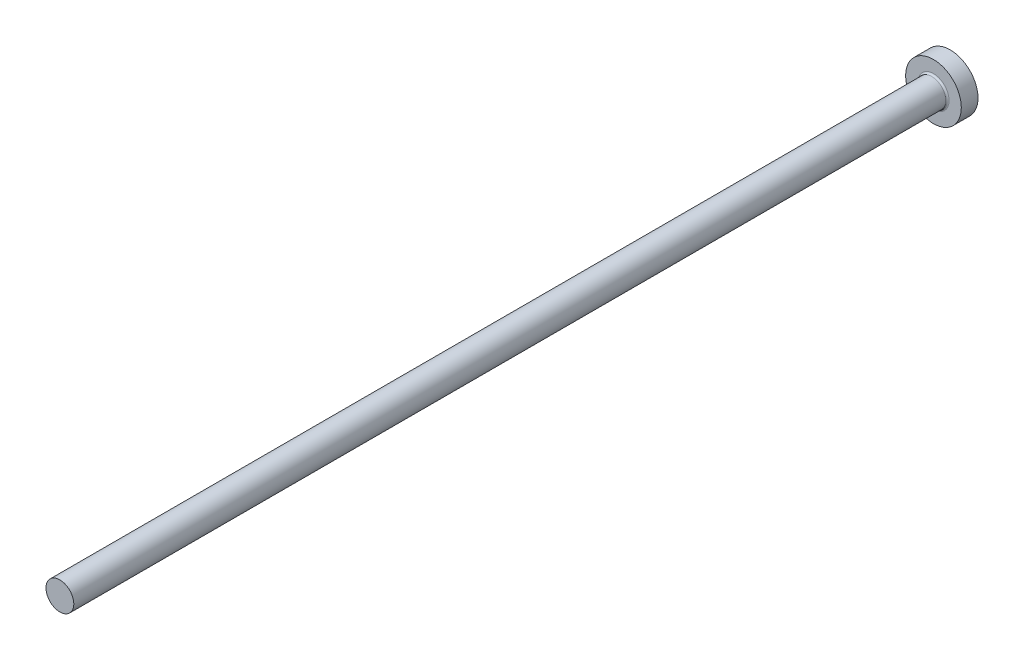
SolidWorks part; units mm, degrees
ref_plane "Płaszczyzna przednia" through (0, 0, 0) normal (0, 0, 1) x (1, 0, 0)
ref_plane "Płaszczyzna górna" through (0, 0, 0) normal (0, 1, 0) x (1, 0, 0)
ref_plane "Płaszczyzna prawa" through (0, 0, 0) normal (1, 0, 0) x (0, 0, -1)
sketch "Szkic1" plane through (0, 0, 0) normal (1, 0, 0) x (0, 0, -1)
  line L0 (-3, 0) -> (-3, 5)
  line L1 (-3, 5) -> (0, 5)
  line L2 (0, 5) -> (0, 0)
  line L3 (0, 0) -> (-3, 0)
  line L4 (0, 0) -> (-3, 0) construction
sketch "Szkic2" plane through (0, 0, 0) normal (1, 0, 0) x (0, 0, -1)
  line L0 (-160, 0) -> (-160, 2.5)
  line L1 (-160, 2.5) -> (-3, 2.5)
  line L2 (-3, 2.5) -> (-3, 0)
  line L3 (-3, 0) -> (-160, 0)
  line L4 (-3, 0) -> (-160, 0) construction
sketch "Szkic3" plane through (0, 0, 0) normal (1, 0, 0) x (0, 0, -1)
  line L0 (-3.3, 2.5) -> (-3, 2.5)
  line L1 (-3, 2.5) -> (-3, 2.8)
  line L2 (0, 0) -> (-3, 0) construction
  arc A0 (-3, 2.8) -> (-3.3, 2.5) centre (-3.3, 2.8) cw
revolve "Obrót1" add sketch "Szkic1" angle 360 about L4 reverse direction yes
revolve "Obrót2" add sketch "Szkic2" angle 360 about L4 reverse direction yes
revolve "Obrót3" add sketch "Szkic3" angle 360 about L2 reverse direction yes
ref_plane "IP1 XY" through (0, 0, 0) normal (0, 0, 1) x (1, 0, 0)
ref_plane "IP1 XZ" through (0, 0, 0) normal (0, -1, 0) x (-1, 0, 0)
ref_plane "IP1 YZ" through (0, 0, 0) normal (1, 0, 0) x (0, 0, -1)
ref_axis "IP1 X" through (-80.9, 0, 0) along (1, 0, 0)
ref_axis "IP1 Y" through (0, -50, 0) along (0, 1, 0)
ref_axis "IP1 Z" through (0, 0, 80.9) along (0, 0, -1)
sketch3d "IP1"
  point P0 (0, 0, 0)
